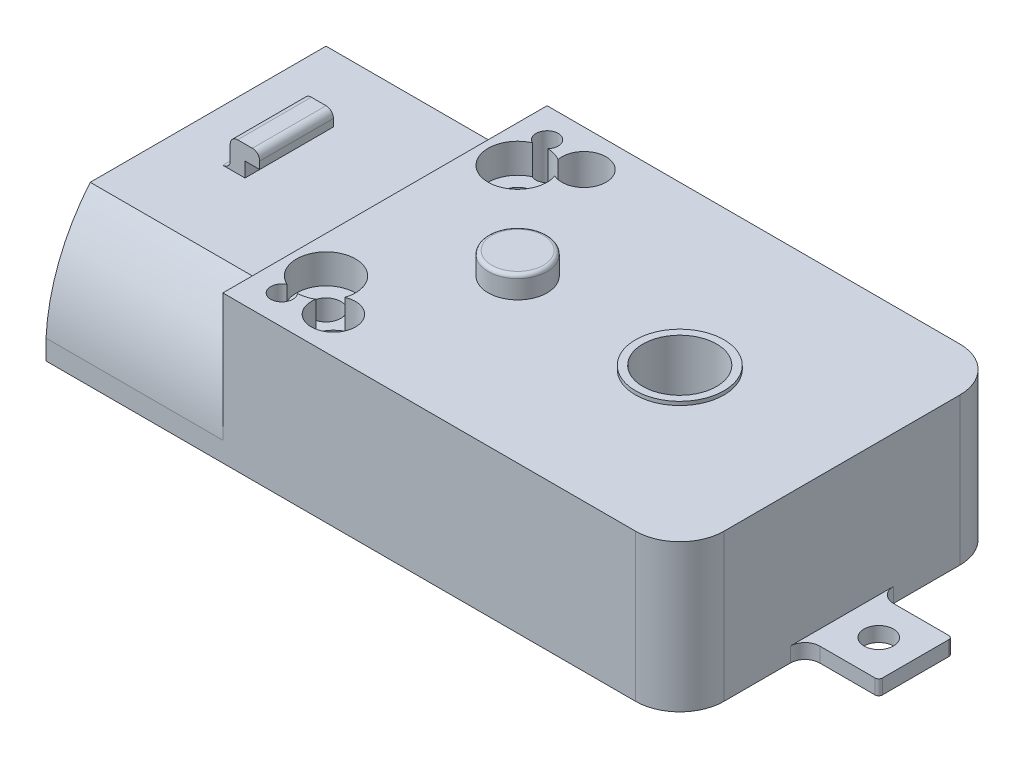
SolidWorks part; units mm, degrees
ref_plane "Front Plane" through (0, 0, 0) normal (0, 0, 1) x (1, 0, 0)
ref_plane "Top Plane" through (0, 0, 0) normal (0, 1, 0) x (1, 0, 0)
ref_plane "Right Plane" through (0, 0, 0) normal (1, 0, 0) x (0, 0, -1)
sketch "Sketch2" plane through (0, 0, 0) normal (0, 1, 0) x (1, 0, 0)
  line L0 (31, 11) -> (0, 11) construction
  line L1 (0, 0) -> (31, 0)
  line L2 (0, 0) -> (0, 22)
  line L3 (0, 22) -> (31, 22)
  line L4 (31, 0) -> (31, 22)
  line L7 (31, 8.5) -> (31, 13.5)
  dimension "48" = 31
  dimension "22" = 22
extrude "Boss-Extrude2" add sketch "Sketch2" along normal blind 9 contours L0 L7 L4 L3 L2 | L4 L0 L2 L1 region at (15.5, 0, -5.5) region at (15.5, 0, -16.5)
sketch "Sketch4" plane through (31, 0, 0) normal (1, 0, 0) x (0, 0, -1)
  line L0 (0, 0) -> (22, 0) construction
  line L1 (8.5, 0) -> (13.5, 0)
  line L2 (8.5, 0) -> (8.5, 1)
  line L3 (8.5, 1) -> (13.5, 1)
  line L4 (13.5, 0) -> (13.5, 1)
  point P6 (11, 1)
  dimension "D1" = 1
  dimension "D2" = 5
  dimension "D3" = 11
extrude "Boss-Extrude3" add sketch "Sketch4" along normal blind 5
sketch "Sketch5" plane through (0, 1, 0) normal (0, 1, 0) x (1, 0, 0)
  circle A0 centre (33.5, 11) radius 1
  dimension "D1" = 2
  dimension "D2" = 2.5
  dimension "D3" = 2.5
extrude "Cut-Extrude1" cut sketch "Sketch5" against normal blind 5
fillet "Fillet1" radius 1 1 edges
fillet "Fillet2" radius 1 1 edges
fillet "Fillet3" radius 3 1 edges at (31, 4.5, 0)
fillet "Fillet4" radius 3 1 edges at (31, 4.5, -22)
sketch "Sketch6" plane through (0, 0, 0) normal (-1, 0, 0) x (0, 0, 1)
  line L0 (-11, 0) -> (-11, 9) construction
  line L1 (0, 0) -> (-22, 0) construction
  line L2 (0, 9) -> (-22, 9) construction
  line L3 (-22, 0) -> (0, 0)
  line L5 (-22, 0) -> (-22.0206, -0.0102)
  line L6 (0, 1.3449) -> (0, 0)
  line L7 (-19, 9) -> (-3, 9)
  line L8 (0, 0) -> (-22, 0)
  arc A0 (0, 0) -> (-3, 9) centre (-12.9826, 0.6725) ccw
  arc A1 (-22, 0) -> (-19, 9) centre (-9.0174, 0.6725) cw
  point P9 (0, 0)
  line M1 (-22, 0) -> (0, 0)
  line M2 (0, 0) -> (0, 9)
  line M3 (0, 9) -> (-22, 9)
  line M4 (-22, 9) -> (-22, 0)
  dimension "D1" = 13
  dimension "D2" = 3
sketch "Sketch7" plane through (0, 0, 0) normal (-1, 0, 0) x (0, 0, 1)
extrude "Boss-Extrude4" add sketch "Sketch6" along normal blind 12 contours L0 L7 A1 M1 M4 | L0 L8 A0 M2 M3 region at (0, 4.2857, -16.1047) region at (0, 4.2857, -5.8953)
fillet "Fillet6" radius 0.25 2 edges at (36, 0.5, -13.5) (36, 0.5, -8.5)
sketch "Sketch10" plane through (0, 9, 0) normal (0, 1, 0) x (1, 0, 0)
  line L0 (-12, 11) -> (30.5, 11) construction
  line L1 (-12, 3) -> (-12, 19) construction
  line L2 (30.5, 3) -> (30.5, 19) construction
  line L4 (28, 0) -> (0, 0) construction
  circle A0 centre (5, 19.5) radius 1.5
  circle A1 centre (5, 2.5) radius 1.5
  dimension "D1" = 3
  dimension "2,5" = 2.5
  dimension "5" = 5
extrude "Cut-Extrude7" cut sketch "Sketch10" against normal through all both and the other way through all
sketch "Sketch12" plane through (0, 9, 0) normal (0, 1, 0) x (1, 0, 0)
  line L0 (28, 0) -> (0, 0) construction
  circle A0 centre (2, 2) radius 0.75
  circle A1 centre (2, 20) radius 0.75
  dimension "D1" = 1.5
  dimension "D2" = 1.5
  dimension "D3" = 2
  dimension "D4" = 2
  dimension "D5" = 2
  dimension "D6" = 2
extrude "Cut-Extrude8" cut sketch "Sketch12" against normal blind 3
sketch "Sketch13" plane through (0, 9, 0) normal (0, 1, 0) x (1, 0, 0)
  line L0 (-12, 11) -> (36, 11) construction
  line L1 (-8, 13.5) -> (-7, 13.5)
  line L2 (-8, 13.5) -> (-8, 8.5)
  line L3 (-8, 8.5) -> (-7, 8.5)
  line L4 (-7, 13.5) -> (-7, 8.5)
  line L5 (-12, 3) -> (-12, 19) construction
  line L6 (36, 13.25) -> (36, 8.75) construction
  dimension "D1" = 4
  dimension "D2" = 1
  dimension "D3" = 5
  dimension "D4" = 2.5
extrude "Boss-Extrude5" add sketch "Sketch13" along normal blind 2
sketch "Sketch14" plane through (-7, 0, 0) normal (1, 0, 0) x (0, 0, -1)
  line L0 (13.5, 11) -> (13.5, 9) construction
  line L1 (8.5, 11) -> (13.5, 11)
  line L2 (8.5, 11) -> (8.5, 10)
  line L3 (8.5, 10) -> (13.5, 10)
  line L4 (13.5, 11) -> (13.5, 10)
extrude "Boss-Extrude6" add sketch "Sketch14" along normal blind 1
fillet "Fillet7" radius 0.5 1 edges at (-8, 11, -11)
fillet "Fillet8" radius 0.5 1 edges at (-8, 9, -11)
fillet "Fillet9" radius 0.5 1 edges at (-6, 11, -11)
sketch "Sketch16" plane through (-12, 0, 0) normal (-1, 0, 0) x (0, 0, 1)
  line L0 (-18.2321, 8.3594) -> (-3.7679, 8.3594)
  line L1 (-21.0013, 1.2932) -> (-21, 0)
  line L2 (-0.9987, 1.2932) -> (-0.9987, 0)
  line L3 (-21, 0) -> (-0.9987, 0)
  arc A2 (-18.2321, 8.3594) -> (-21.0013, 1.2932) centre (-9.0174, 0.6725) ccw
  arc A3 (-18.2321, 8.3594) -> (-21.0013, 1.2932) centre (-9.0174, 0.6725) ccw
  arc A5 (-0.9987, 1.2932) -> (-3.7679, 8.3594) centre (-12.9826, 0.6725) ccw
  arc A6 (-0.9987, 1.2932) -> (-3.7679, 8.3594) centre (-12.9826, 0.6725) ccw
  dimension "D1" = 1
  dimension "D2" = 1
extrude "Cut-Extrude9" cut sketch "Sketch16" against normal blind 10
sketch "Sketch17" plane through (0, 9, 0) normal (0, 1, 0) x (1, 0, 0)
  line L0 (0, 3) -> (0, 19)
  line L8 (31, 3) -> (31, 19)
  line L9 (28, 22) -> (0, 22)
  line L10 (0, 22) -> (0, 19)
  line L11 (0, 19) -> (-12, 19)
  line L12 (-12, 19) -> (-12, 3)
  line L13 (-12, 3) -> (0, 3)
  line L14 (0, 3) -> (0, 0)
  line L15 (0, 0) -> (28, 0)
  line L16 (31, 3) -> (31, 19)
  line L17 (28, 22) -> (0, 22)
  line L18 (0, 22) -> (0, 19)
  line L22 (0, 3) -> (0, 0)
  line L23 (0, 0) -> (28, 0)
  arc A2 (31, 19) -> (28, 22) centre (28, 19) ccw
  arc A3 (28, 0) -> (31, 3) centre (28, 3) ccw
  arc A4 (31, 19) -> (28, 22) centre (28, 19) ccw
  arc A5 (28, 0) -> (31, 3) centre (28, 3) ccw
  dimension "D1" = 0
extrude "Boss-Extrude7" add sketch "Sketch17" along normal blind 1
sketch "Sketch18" plane through (0, 10, 0) normal (0, 1, 0) x (1, 0, 0)
  line L0 (0, 11) -> (31, 11) construction
  line L1 (0, 19) -> (0, 3) construction
  line L2 (31, 3) -> (31, 19) construction
  circle A1 centre (5, 19.5) radius 1.5
  circle A3 centre (5, 2.5) radius 1.5
  dimension "D3" = 2.5
  dimension "D8" = 5
  dimension "3" = 3
  dimension "D10" = 3
  dimension "D2" = 2.5
  dimension "D9" = 5
extrude "Cut-Extrude12" cut sketch "Sketch18" against normal through all
sketch "Sketch19" plane through (0, 10, 0) normal (0, 1, 0) x (1, 0, 0)
  line L0 (0, 11) -> (31, 11) construction
  line L1 (0, 22) -> (0, 0) construction
  line L2 (31, 3) -> (31, 19) construction
  circle A0 centre (2, 20) radius 0.75
  circle A1 centre (2, 2) radius 0.75
  dimension "D1" = 1.5
  dimension "D2" = 1.5
  dimension "D3" = 2
  dimension "2" = 2
  dimension "D4" = 2
  dimension "D5" = 2
extrude "Cut-Extrude14" cut sketch "Sketch19" against normal through all
sketch "Sketch20" plane through (0, 10, 0) normal (0, 1, 0) x (1, 0, 0)
  line L0 (0, 11) -> (31, 11) construction
  line L1 (0, 22) -> (0, 0) construction
  line L2 (31, 3) -> (31, 19) construction
  circle A0 centre (9, 11) radius 2
  dimension "D2" = 4
  dimension "D1" = 22
extrude "Boss-Extrude8" add sketch "Sketch20" along normal blind 1.5
fillet "Fillet10" radius 0.25 1 edges at (9, 11.5, -9)
sketch "Sketch21" plane through (0, 10, 0) normal (0, 1, 0) x (1, 0, 0)
  line L0 (0, 11) -> (31, 11) construction
  line L1 (0, 19) -> (0, 3) construction
  line L2 (31, 3) -> (31, 19) construction
  circle A0 centre (20, 11) radius 2.5
  dimension "D1" = 11
  dimension "6" = 5
extrude "Cut-Extrude15" cut sketch "Sketch21" against normal blind 5
sketch "Sketch22" plane through (0, 10, 0) normal (0, 1, 0) x (1, 0, 0)
  circle A0 centre (20, 11) radius 3
  circle A1 centre (20, 11) radius 2.5
  dimension "D1" = 6
  dimension "D2" = 5
extrude "Boss-Extrude9" add sketch "Sketch22" along normal blind 0.25
sketch "Sketch24" plane through (0, 10, 0) normal (0, 1, 0) x (1, 0, 0)
  line L0 (0, 11) -> (36, 11) construction
  line L1 (0, 19) -> (0, 3) construction
  line L2 (36, 13.25) -> (36, 8.75) construction
  circle A0 centre (2.5, 17.5) radius 2
  circle A1 centre (2.5, 4.5) radius 2
  dimension "D1" = 4
  dimension "D2" = 2.5
  dimension "D3" = 4.5
extrude "Cut-Extrude16" cut sketch "Sketch24" against normal blind 2
sketch "Sketch25" plane through (0, 10, 0) normal (0, 1, 0) x (1, 0, 0)
  circle A0 centre (2.5, 17.5) radius 1
  circle A1 centre (2.5, 4.5) radius 1
  dimension "D1" = 2
  dimension "D2" = 2
extrude "Cut-Extrude17" cut sketch "Sketch25" against normal blind 5
